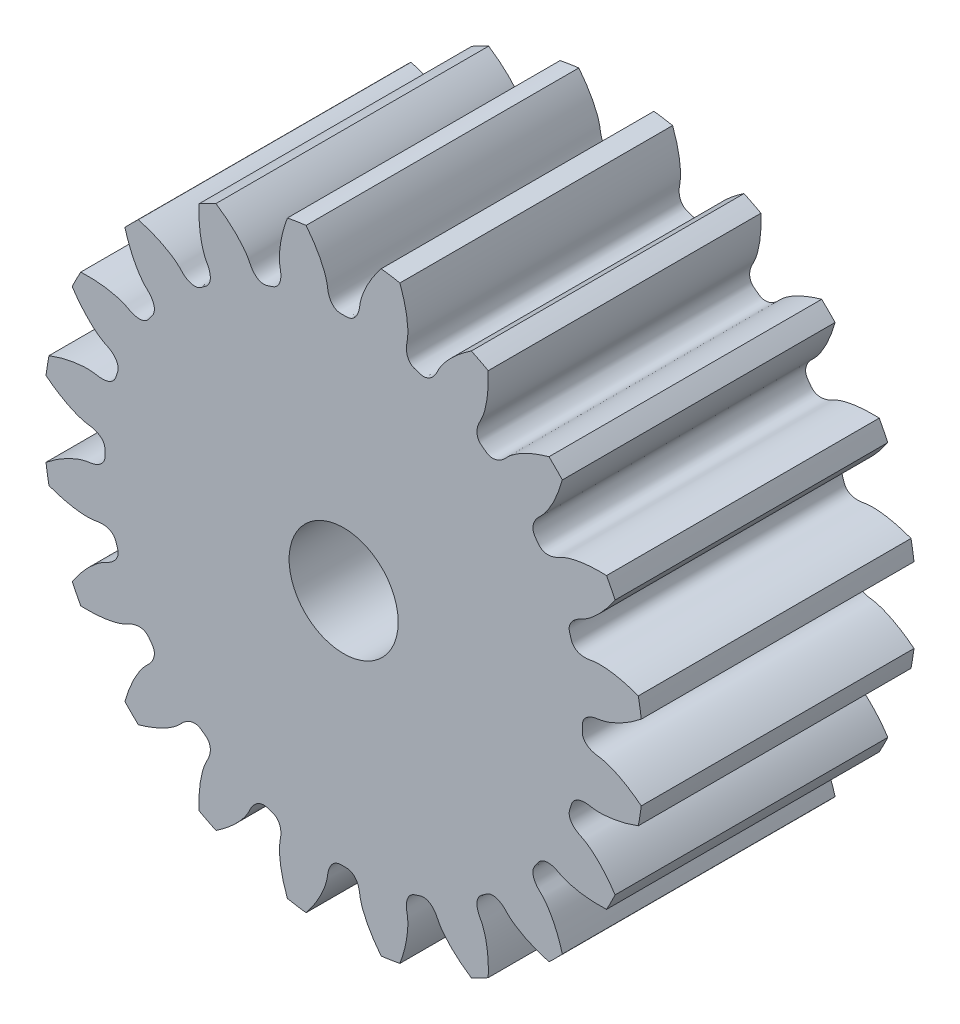
SolidWorks part; units mm, degrees
ref_plane "前视基准面" through (0, 0, 0) normal (0, 0, 1) x (1, 0, 0)
ref_plane "上视基准面" through (0, 0, 0) normal (0, 1, 0) x (1, 0, 0)
ref_plane "右视基准面" through (0, 0, 0) normal (1, 0, 0) x (0, 0, -1)
ref_axis "基准轴1" through (0, 0, 55) along (0, 0, -1)
sketch "SketchRevolveSpurGear1" plane through (0, 0, 0) normal (1, 0, 0) x (0, 0, -1)
  line L0 (0, 0) -> (1, 0) construction
  line L1 (-2.5, 0) -> (-2.5, 5.5)
  line L2 (-2.5, 5.5) -> (2.5, 5.5)
  line L3 (2.5, 5.5) -> (2.5, 0)
  line L4 (2.5, 0) -> (-2.5, 0)
revolve "SpurGear1" add sketch "SketchRevolveSpurGear1" angle 360 about L0
sketch "SketchToothSpurGear1" plane through (0, 0, 0) normal (0, 0, 1) x (1, 0, 0)
  arc A0 (5.4796, 0.7068) -> (5.4796, -0.7068) centre (0, 0) cw
  spline S0 degree 3 poles (5.4796, -0.7068) (5.4354, -0.6709) (5.3693, -0.6203) (5.2806, -0.5589) (5.2183, -0.5186) (5.1586, -0.4825) (5.1018, -0.4505) (5.048, -0.4224) (4.9974, -0.3979) (4.9502, -0.3768) (4.9065, -0.3589) (4.8665, -0.3439) (4.8303, -0.3316) (4.7981, -0.3218) (4.7699, -0.3141) (4.7458, -0.3083) (4.726, -0.3042) (4.6831, -0.2968) (4.6374, -0.2927) (4.5899, -0.2809) (4.5652, -0.2735) (4.5415, -0.265) (4.5186, -0.2551) (4.4964, -0.2437) (4.4749, -0.2304) (4.4541, -0.2149) (4.434, -0.1964) (4.4151, -0.1743) (4.3981, -0.148) (4.3844, -0.117) (4.3768, -0.0845) (4.3736, -0.045) (4.3759, 0) (4.3736, 0.045) (4.3768, 0.0845) (4.3844, 0.117) (4.3981, 0.148) (4.4151, 0.1743) (4.434, 0.1964) (4.4541, 0.2149) (4.4749, 0.2304) (4.4964, 0.2437) (4.5186, 0.2551) (4.5415, 0.265) (4.5652, 0.2735) (4.5899, 0.2809) (4.6374, 0.2927) (4.6831, 0.2968) (4.726, 0.3042) (4.7458, 0.3083) (4.7699, 0.3141) (4.7981, 0.3218) (4.8303, 0.3316) (4.8665, 0.3439) (4.9065, 0.3589) (4.9502, 0.3768) (4.9974, 0.3979) (5.048, 0.4224) (5.1018, 0.4505) (5.1586, 0.4825) (5.2183, 0.5186) (5.2806, 0.5589) (5.3693, 0.6203) (5.4354, 0.6709) (5.4796, 0.7068) knots 0 0 0 0 0.061423 0.08971 0.11638 0.141434 0.164872 0.186693 0.206898 0.225486 0.242459 0.257814 0.271554 0.283677 0.294183 0.303073 0.310347 0.316004 0.350077 0.359568 0.368803 0.377844 0.386769 0.395676 0.404689 0.413963 0.423683 0.434051 0.445256 0.457401 0.47042 0.481067 0.5 0.518933 0.52958 0.542599 0.554744 0.565949 0.576317 0.586037 0.595311 0.604324 0.613231 0.622156 0.631197 0.640432 0.649923 0.683996 0.689653 0.696927 0.705817 0.716323 0.728446 0.742186 0.757541 0.774514 0.793102 0.813307 0.835128 0.858566 0.88362 0.91029 0.938577 1 1 1 1
extrude "ToothExtrudeCutSpurGear1" cut sketch "SketchToothSpurGear1" against normal blind 2.5 and the other way blind 2.5
pattern_circular "PatternSpurGear1" count 20 every 18 about axis through (0, 0, 55) along (0, 0, -1) of "ToothExtrudeCutSpurGear1"
sketch "BoreRevolveSketch" plane through (0, 0, 0) normal (1, 0, 0) x (0, 0, -1)
  line L0 (0, 0) -> (1, 0) construction
  line L1 (-2.5, 0) -> (2.5, 0)
  line L2 (2.5, 0) -> (2.5, 1)
  line L3 (2.5, 1) -> (-2.5, 1)
  line L4 (-2.5, 1) -> (-2.5, 0)
  dimension "TaperSide1" = 1
  dimension "TaperSide2" = 1
revolve "BoreRevolveCut" cut sketch "BoreRevolveSketch" angle 360 about L0
sketch "AuxiliarySketchSpurGear1" plane through (0, 0, 0) normal (0, 0, 1) x (1, 0, 0)
  circle A0 centre (0, 0) radius 5 construction
  circle A1 centre (0, 0) radius 4.6985 construction
  circle A2 centre (0, 0) radius 4.7016 construction
  circle A3 centre (0, 0) radius 5.5 construction
  circle A4 centre (0, 0) radius 4.375 construction
  dimension "PitchDiameter" = 10
  dimension "BaseDiameter" = 9.3969
  dimension "FormDiameter" = 9.4032
  dimension "MajorDiameter" = 11
  dimension "MinorDiameter" = 8.75
